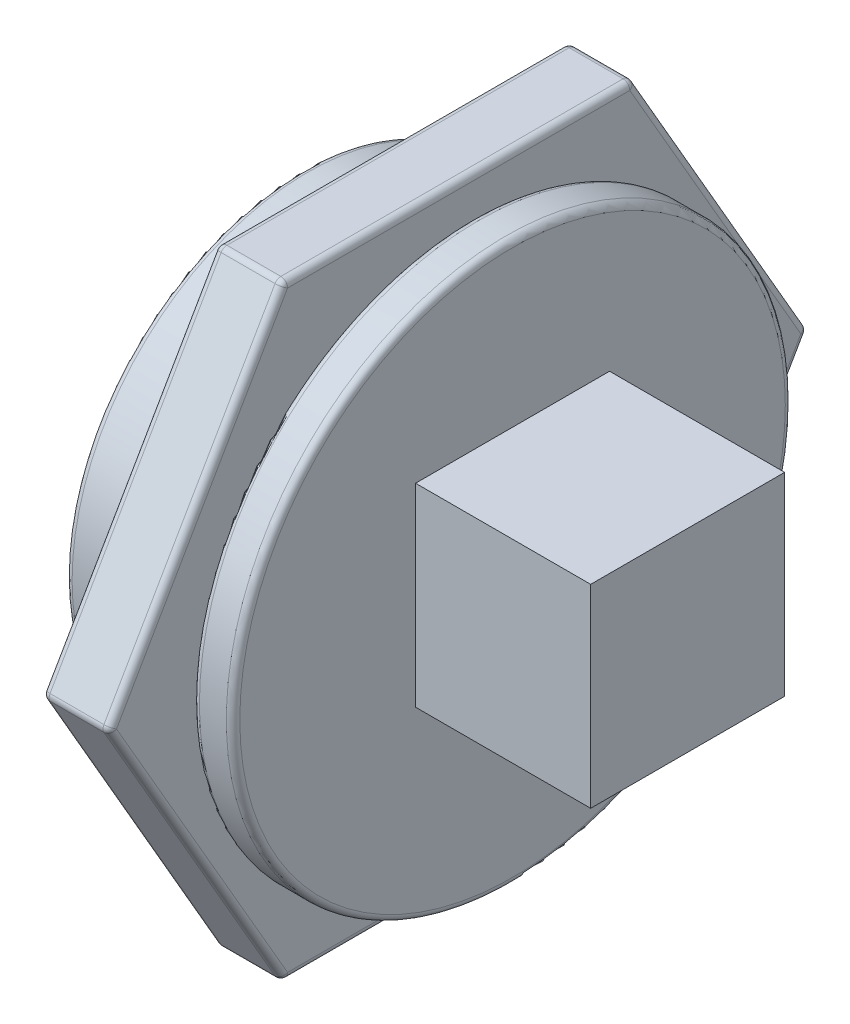
SolidWorks part; units mm, degrees
ref_plane "Plan de face" through (0, 0, 0) normal (0, 0, 1) x (1, 0, 0)
ref_plane "Plan de dessus" through (0, 0, 0) normal (0, 1, 0) x (1, 0, 0)
ref_plane "Plan de droite" through (0, 0, 0) normal (1, 0, 0) x (0, 0, -1)
sketch "Esquisse1" plane through (0, 0, 0) normal (0, 0, 1) x (1, 0, 0)
  line L0 (15.223, 0) -> (-20.2974, 0) construction
  line L1 (-12.7, 0) -> (-12.7, 17.5)
  line L2 (-12.7, 17.5) -> (0, 17.5)
  line L3 (0, 17.5) -> (0, 20.75)
  line L4 (0, 20.75) -> (3, 20.75)
  line L5 (3, 20.75) -> (3, 0)
  line L6 (3, 0) -> (-12.7, 0)
  dimension "D1" = 35
  dimension "D2" = 41.5
  dimension "D3" = 3
  dimension "D4" = 12.7
revolve "Révolution1" add sketch "Esquisse1" angle 360 about L0
sketch "Esquisse2" plane through (0, 0, 0) normal (-1, 0, 0) x (0, 0, 1)
  line L1 (12.9904, -22.5) -> (25.9808, 0)
  line L2 (25.9808, 0) -> (12.9904, 22.5)
  line L3 (12.9904, 22.5) -> (-12.9904, 22.5)
  line L4 (-12.9904, 22.5) -> (-25.9808, 0)
  line L5 (-25.9808, 0) -> (-12.9904, -22.5)
  line L6 (-12.9904, -22.5) -> (12.9904, -22.5)
  circle A0 centre (0, 0) radius 22.5 construction
  dimension "D1" = 45
extrude "Boss.-Extru.1" add sketch "Esquisse2" along normal blind 5 from offset 1
sketch "Esquisse3" plane through (3, 0, 0) normal (1, 0, 0) x (0, 0, -1)
  line L1 (-7.2, 8.7) -> (7.2, 8.7)
  line L2 (-7.2, 8.7) -> (-7.2, -5.7)
  line L3 (-7.2, -5.7) -> (7.2, -5.7)
  line L4 (7.2, 8.7) -> (7.2, -5.7)
  line L5 (-7.2, 8.7) -> (7.2, -5.7) construction
  line L6 (-7.2, -5.7) -> (7.2, 8.7) construction
  point P0 (0, 1.5)
  dimension "D1" = 14.4
  dimension "D2" = 5.7
extrude "Boss.-Extru.2" add sketch "Esquisse3" along normal offset from surface (13 mm away) 16 up to face at (0, 0, -17.5)
fillet "Congé1" radius 0.5 23 edges at (-1, 0, 17.5) (0, 0, -17.5) (-6, -11.25, -19.4856) (-1, -11.25, -19.4856) (-3.5, -22.5, -12.9904) (-6, -22.5, 0) (-1, -22.5, 0) (-3.5, -22.5, 12.9904) (-6, -11.25, 19.4856) (-1, -11.25, 19.4856) (-3.5, 0, 25.9808) (-6, 11.25, 19.4856) (-1, 11.25, 19.4856) (-3.5, 22.5, 12.9904) (-6, 22.5, 0) (-1, 22.5, 0) (-3.5, 22.5, -12.9904) (-6, 11.25, -19.4856) (-3.5, 0, -25.9808) (-1, 11.25, -19.4856) (-12.7, 0, -17.5) (3, 0, -20.75) (0, 0, -20.75)
sketch "Esquisse4" plane through (-12.7, 0, 0) normal (-1, 0, 0) x (0, 0, 1)
  line L0 (7.2, -5.7) -> (-7.2, -5.7) construction
  line L1 (-7, 8.5) -> (7, 8.5)
  line L2 (-7, 8.5) -> (-7, -5.5)
  line L3 (-7, -5.5) -> (7, -5.5)
  line L4 (7, 8.5) -> (7, -5.5)
  line L5 (-7, 8.5) -> (7, -5.5) construction
  line L6 (-7, -5.5) -> (7, 8.5) construction
  point P0 (0, 1.5)
  dimension "D1" = 14
  dimension "D2" = 0.2
extrude "Enlèv. mat.-Extru.1" cut sketch "Esquisse4" against normal blind 16
